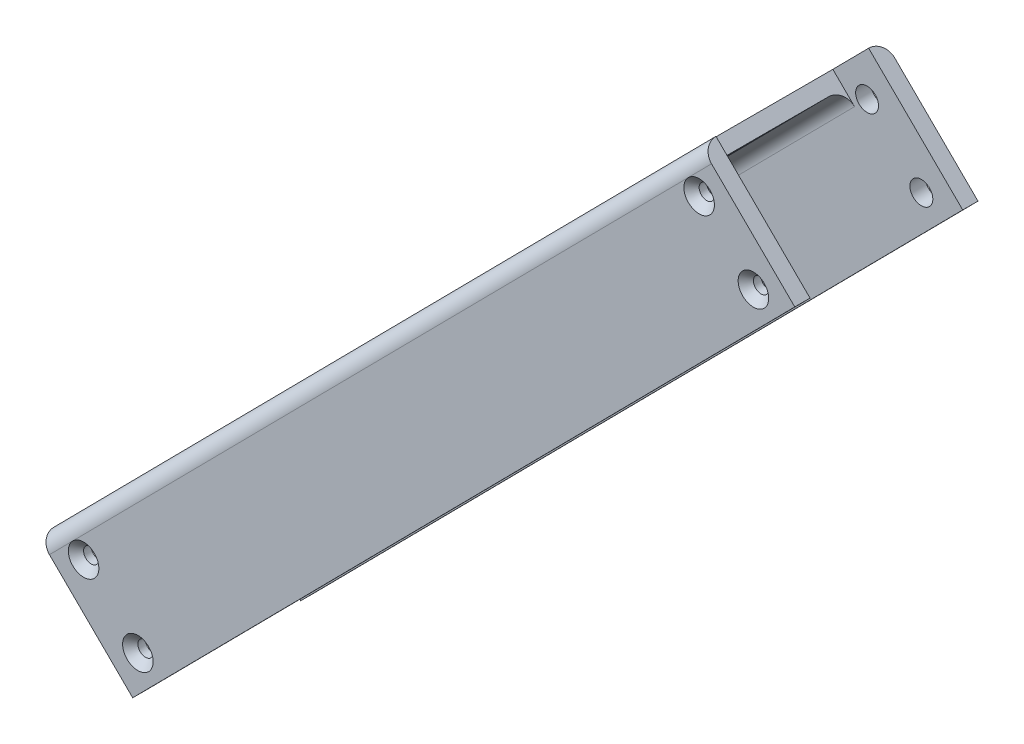
SolidWorks part; units mm, degrees
ref_plane "Front Plane" through (0, 0, 0) normal (0, 0, 1) x (1, 0, 0)
ref_plane "Top Plane" through (0, 0, 0) normal (0, 1, 0) x (1, 0, 0)
ref_plane "Right Plane" through (0, 0, 0) normal (1, 0, 0) x (0, 0, -1)
sketch "Sketch2" plane through (0, 0, 0) normal (0, 0, 1) x (1, 0, 0)
  line L0 (165.715, 148.457) -> (35.6364, 16.9102)
  line L1 (35.6364, 16.9102) -> (54.1241, -1.3711)
  line L4 (54.1241, -1.3711) -> (184.2027, 130.1757)
  line L25 (165.715, 148.457) -> (184.2027, 130.1757)
extrude "Boss-Extrude1" add sketch "Sketch2" against normal blind 3
sketch "Sketch4" plane through (0, 0, -36) normal (0, 0, -1) x (-1, 0, 0)
  line L6 (-165.715, 148.457) -> (-184.2027, 130.1757)
  line L9 (-184.2027, 130.1757) -> (-54.1241, -1.3711)
  line L10 (-54.1241, -1.3711) -> (-35.6364, 16.9102)
  line L11 (-35.6364, 16.9102) -> (-165.715, 148.457)
  line L12 (-165.715, 148.457) -> (-184.2027, 130.1757)
  line L15 (-184.2027, 130.1757) -> (-54.1241, -1.3711)
  line L16 (-54.1241, -1.3711) -> (-35.6364, 16.9102)
  line L17 (-35.6364, 16.9102) -> (-165.715, 148.457)
  dimension "D1" = 0
extrude "Boss-Extrude2" add sketch "Sketch4" against normal blind 3 separate body
sketch "Sketch5" plane through (0, 0, -3) normal (0, 0, -1) x (-1, 0, 0)
  line L0 (-35.6364, 16.9102) -> (-165.715, 148.457) construction
  line L1 (-35.6364, 16.9102) -> (-165.715, 148.457)
  line L2 (-37.7696, 14.8008) -> (-167.8482, 146.3476)
  line L3 (-37.7696, 14.8008) -> (-35.6364, 16.9102)
  line L4 (-167.8482, 146.3476) -> (-165.715, 148.457)
  dimension "D1" = 3
extrude "Boss-Extrude3" add sketch "Sketch5" along normal up to surface (30 mm away) up to face at (109.9195, 73.543, -33)
fillet "Fillet1" radius 3 4 edges at (102.8089, 80.5742, -3) (102.8089, 80.5742, -33) (100.6757, 82.6836, -36) (100.6757, 82.6836, 0)
sketch "Sketch6" plane through (9.5636, -9.4569, 0) normal (-0.7111, 0.7031, 0) x (0, 0, 1)
  circle A0 centre (-18, 197.0812) radius 7.5
extrude "Cut-Extrude1" cut sketch "Sketch6" against normal up to surface (3 mm away) up to face at (102.8089, 80.5742, -18)
sketch "Sketch7" plane through (9.5636, -9.4569, 0) normal (-0.7111, 0.7031, 0) x (0, 0, 1)
  line L5 (-3, 37.0812) -> (-3, 222.0812) construction
  line L6 (-3, 212.0812) -> (-3, 222.0812)
  line L7 (-33, 222.0812) -> (-33, 37.0812) construction
  line L8 (-33, 222.0812) -> (-33, 212.0812)
  line L9 (-33, 212.0812) -> (-3, 212.0812)
  line L12 (-33, 222.0812) -> (-3, 222.0812)
  line L13 (-36, 129.5812) -> (0, 129.5812) construction
  line L14 (-36, 37.0812) -> (-36, 222.0812) construction
  line L15 (0, 222.0812) -> (0, 37.0812) construction
  line L16 (-33, 37.0812) -> (-3, 37.0812)
  line L17 (-33, 47.0812) -> (-3, 47.0812)
  line L18 (-33, 37.0812) -> (-33, 47.0812)
  line L19 (-3, 47.0812) -> (-3, 37.0812)
extrude "Cut-Extrude2" cut sketch "Sketch7" against normal up to surface (26 mm away) up to face at (119.1634, 64.4023, -1.5)
sketch "Sketch8" plane through (0, 0, 0) normal (0, 0, 1) x (1, 0, 0)
  line L0 (58.6944, 3.2508) -> (40.2067, 21.5321) construction
  line L5 (179.6323, 125.5538) -> (161.1447, 143.8351) construction
  line L6 (158.6837, 141.3464) -> (165.715, 148.457) construction
  line L8 (100.6757, 82.6836) -> (119.1634, 64.4023) construction
  line L9 (42.6677, 24.0208) -> (158.6837, 141.3464) construction
  line L10 (54.1241, -1.3711) -> (184.2027, 130.1757) construction
  circle A0 centre (176.077, 129.0694) radius 1.5
  circle A1 centre (165.4111, 139.6163) radius 1.5
  circle A2 centre (44.4731, 17.3134) radius 1.5
  circle A3 centre (55.1391, 6.7664) radius 1.5
extrude "Cut-Extrude3" cut sketch "Sketch8" against normal blind 3
sketch "Sketch9" plane through (0, 0, -36) normal (0, 0, -1) x (-1, 0, 0)
  circle A0 centre (-165.4111, 139.6163) radius 2.25
  circle A1 centre (-176.077, 129.0694) radius 2.25
  circle A2 centre (-44.4731, 17.3134) radius 2.25
  circle A3 centre (-55.1391, 6.7664) radius 2.25
extrude "Cut-Extrude4" cut sketch "Sketch9" against normal blind 3
chamfer "Chamfer1" distance 1.5 angle 45 4 edges at (42.9731, 17.3134, 0) (53.6391, 6.7664, 0) (177.577, 129.0694, 0) (166.9111, 139.6163, 0)
fillet "Fillet2" radius 1 2 edges at (142.8634, 125.3474, -18) (144.9966, 123.2381, -18)
